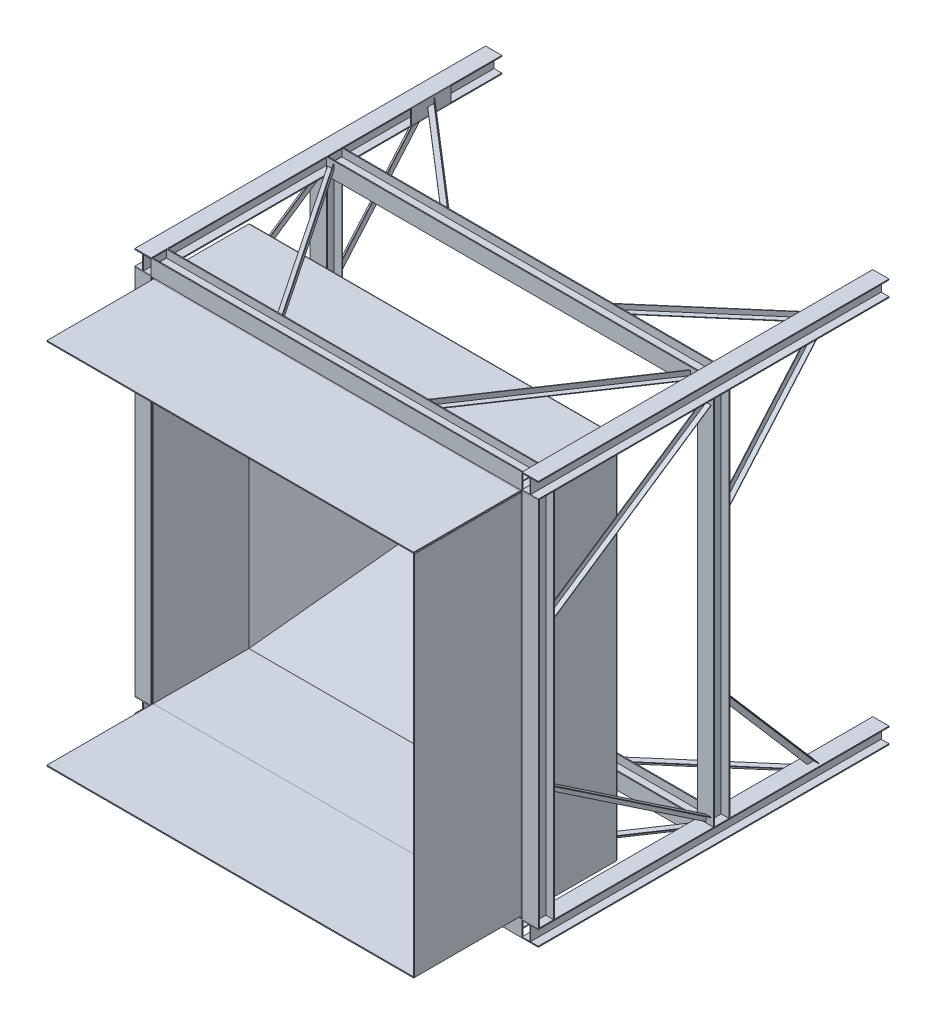
SolidWorks part; units mm, degrees
other "DetailItem1"
other "DetailItem2"
other "DetailItem3"
other "DetailItem4"
other "DetailItem5"
other "DetailItem6"
other "DetailItem7"
other "DetailItem8"
other "DetailItem9"
other "DetailItem10"
other "DetailItem11"
other "DetailItem12"
other "DetailItem13"
other "DetailItem14"
other "DetailItem15"
other "DetailItem16"
other "DetailItem17"
other "DetailItem18"
other "DetailItem19"
other "DetailItem20"
other "DetailItem21"
other "DetailItem22"
other "DetailItem23"
other "DetailItem24"
other "DetailItem25"
other "DetailItem26"
other "DetailItem27"
other "DetailItem28"
other "DetailItem29"
other "DetailItem30"
other "DetailItem31"
other "DetailItem32"
other "DetailItem33"
other "DetailItem34"
other "DetailItem35"
other "DetailItem36"
other "DetailItem37"
other "DetailItem38"
other "DetailItem39"
other "DetailItem40"
other "DetailItem41"
other "DetailItem42"
other "DetailItem43"
other "DetailItem44"
other "DetailItem45"
other "DetailItem46"
other "DetailItem47"
other "DetailItem48"
other "DetailItem49"
other "DetailItem50"
other "DetailItem51"
other "DetailItem52"
other "DetailItem53"
other "DetailItem54"
other "DetailItem55"
other "DetailItem56"
other "DetailItem57"
other "DetailItem58"
other "DetailItem59"
other "DetailItem60"
other "DetailItem61"
other "DetailItem62"
other "DetailItem63"
other "DetailItem64"
other "DetailItem65"
other "DetailItem66"
other "DetailItem67"
other "DetailItem68"
other "DetailItem69"
other "DetailItem70"
other "DetailItem71"
other "DetailItem72"
other "DetailItem73"
other "Carpeta de soldadura"
other "Cordón de soldadura1"
other "Soldadura Viga H carga 1650 B"
other "Soldadura Viga H carga 3300 A"
other "Soldadura Viga H carga 3300 B"
other "Soldadura asiento a tolva carga"
other "Soldadura asiento a bastidor carga"
other "Soldadura Viga H fondo 1650 A"
other "Soldadura Viga H fondo 1650 B"
other "Soldadura Viga H fondo 3300 A"
other "Soldadura Viga H fondo 3300 B"
other "Soldadura asiento a tolva fondo"
other "Soldadura asiento a bastidor fondo"
other "Soldadura Viga H izquierda 1650 A"
other "Soldadura Viga H izquierda 1650 B"
other "Soldadura Viga H izquierda 3300 A"
other "Soldadura Viga H izquierda 3300 B"
other "Soldadura asiento a tolva izquierda"
other "Soldadura asiento a bastidor izquierda"
other "Soldadura Viga H derecha 1650 A"
other "Soldadura Viga H derecha 1650 B"
other "Soldadura Viga H derecha 3300 A"
other "Soldadura Viga H derecha 3300 B"
other "Soldadura asiento a tolva derecha"
other "Soldadura asiento a bastidor derecha"
other "Soldadura Angular superior carga A inferior"
other "Soldadura Angular superior carga A superior"
other "Soldadura Angular inferior carga A inferior"
other "Soldadura Angular inferior carga A superior"
other "Soldadura Angular superior carga B inferior"
other "Soldadura Angular superior carga B superior"
other "Soldadura Angular inferior carga B inferior"
other "Soldadura Angular inferior carga B superior"
other "Soldadura Angular superior fondo A inferior"
other "Soldadura Angular superior fondo A superior"
other "Soldadura Angular inferior fondo A inferior"
other "Soldadura Angular inferior fondo A superior"
other "Soldadura Angular superior fondo B inferior"
other "Soldadura Angular superior fondo B superior"
other "Soldadura Angular inferior fondo B inferior"
other "Soldadura Angular inferior fondo B superior"
other "Soldadura Angular superior izquierda A inferior"
other "Soldadura Angular superior izquierda A superior"
other "Soldadura Angular inferior izquierda A inferior"
other "Soldadura Angular inferior izquierda A superior"
other "Soldadura Angular superior izquierda B inferior"
other "Soldadura Angular superior izquierda B superior"
other "Soldadura Angular inferior izquierda B inferior"
other "Soldadura Angular inferior izquierda B superior"
other "Soldadura Angular superior derecha A inferior"
other "Soldadura Angular superior derecha A superior"
other "Soldadura Angular inferior derecha A inferior"
other "Soldadura Angular inferior derecha A superior"
other "Soldadura Angular superior derecha B inferior"
other "Soldadura Angular superior derecha B superior"
other "Soldadura Angular inferior derecha B inferior"
other "Soldadura Angular inferior derecha B superior"
other "Soldadura alerón a collar lateral Y negativo"
other "Soldadura esquina del collar lateral Y negativo"
other "Soldadura quiebre del embudo lateral Y negativo"
other "Soldadura arista inclinada lateral Y negativo"
other "Soldadura alerón a collar derecha"
other "Soldadura esquina del collar derecha"
other "Soldadura quiebre del embudo derecha"
other "Soldadura arista inclinada derecha"
other "Soldadura alerón a collar lateral Y positivo"
other "Soldadura esquina del collar lateral Y positivo"
other "Soldadura quiebre del embudo lateral Y positivo"
other "Soldadura arista inclinada lateral Y positivo"
other "Soldadura esquina del collar carga"
other "Soldadura quiebre del embudo carga"
other "Soldadura arista inclinada carga"
other "Soldadura esquina alerones derecha"
other "Soldadura esquina alerones sur"
material "ASTM A36 Steel"
ref_plane "Front Plane" through (0, 0, 0) normal (0, 0, 1) x (1, 0, 0)
ref_plane "Top Plane" through (0, 0, 0) normal (0, 1, 0) x (1, 0, 0)
ref_plane "Right Plane" through (0, 0, 0) normal (1, 0, 0) x (0, 0, -1)
sketch3d "Referencias 1"
  point P0 (0, 0, 0)
  point P1 (0, -190, 0)
  point P2 (200, 0, 0)
ref_plane "Plano de perfil 1 estructura" through (0, 0, 0) normal (0, 0, 1) x (1, 0, 0)
sketch "Contorno Columna H 1" plane through (0, 0, 0) normal (0, 0, 1) x (1, 0, 0)
  line L0 (-1898, -1898) -> (-1745, -1898)
  line L1 (-1745, -1898) -> (-1745, -1889)
  line L2 (-1745, -1889) -> (-1818.25, -1889)
  line L3 (-1818.25, -1889) -> (-1818.25, -1754)
  line L4 (-1818.25, -1754) -> (-1745, -1754)
  line L5 (-1745, -1754) -> (-1745, -1745)
  line L6 (-1745, -1745) -> (-1898, -1745)
  line L7 (-1898, -1745) -> (-1898, -1754)
  line L8 (-1898, -1754) -> (-1824.75, -1754)
  line L9 (-1824.75, -1754) -> (-1824.75, -1889)
  line L10 (-1824.75, -1889) -> (-1898, -1889)
  line L11 (-1898, -1889) -> (-1898, -1898)
extrude "Columna H 1" add sketch "Contorno Columna H 1" along normal blind 3300 separate body
sketch "Contorno Columna H 2" plane through (0, 0, 0) normal (0, 0, 1) x (1, 0, 0)
  line L0 (-1898, 1745) -> (-1745, 1745)
  line L1 (-1745, 1745) -> (-1745, 1754)
  line L2 (-1745, 1754) -> (-1818.25, 1754)
  line L3 (-1818.25, 1754) -> (-1818.25, 1889)
  line L4 (-1818.25, 1889) -> (-1745, 1889)
  line L5 (-1745, 1889) -> (-1745, 1898)
  line L6 (-1745, 1898) -> (-1898, 1898)
  line L7 (-1898, 1898) -> (-1898, 1889)
  line L8 (-1898, 1889) -> (-1824.75, 1889)
  line L9 (-1824.75, 1889) -> (-1824.75, 1754)
  line L10 (-1824.75, 1754) -> (-1898, 1754)
  line L11 (-1898, 1754) -> (-1898, 1745)
extrude "Columna H 2" add sketch "Contorno Columna H 2" along normal blind 3300 separate body
sketch "Contorno Columna H 3" plane through (0, 0, 0) normal (0, 0, 1) x (1, 0, 0)
  line L0 (1745, -1898) -> (1898, -1898)
  line L1 (1898, -1898) -> (1898, -1889)
  line L2 (1898, -1889) -> (1824.75, -1889)
  line L3 (1824.75, -1889) -> (1824.75, -1754)
  line L4 (1824.75, -1754) -> (1898, -1754)
  line L5 (1898, -1754) -> (1898, -1745)
  line L6 (1898, -1745) -> (1745, -1745)
  line L7 (1745, -1745) -> (1745, -1754)
  line L8 (1745, -1754) -> (1818.25, -1754)
  line L9 (1818.25, -1754) -> (1818.25, -1889)
  line L10 (1818.25, -1889) -> (1745, -1889)
  line L11 (1745, -1889) -> (1745, -1898)
extrude "Columna H 3" add sketch "Contorno Columna H 3" along normal blind 3300 separate body
sketch "Contorno Columna H 4" plane through (0, 0, 0) normal (0, 0, 1) x (1, 0, 0)
  line L0 (1745, 1745) -> (1898, 1745)
  line L1 (1898, 1745) -> (1898, 1754)
  line L2 (1898, 1754) -> (1824.75, 1754)
  line L3 (1824.75, 1754) -> (1824.75, 1889)
  line L4 (1824.75, 1889) -> (1898, 1889)
  line L5 (1898, 1889) -> (1898, 1898)
  line L6 (1898, 1898) -> (1745, 1898)
  line L7 (1745, 1898) -> (1745, 1889)
  line L8 (1745, 1889) -> (1818.25, 1889)
  line L9 (1818.25, 1889) -> (1818.25, 1754)
  line L10 (1818.25, 1754) -> (1745, 1754)
  line L11 (1745, 1754) -> (1745, 1745)
extrude "Columna H 4" add sketch "Contorno Columna H 4" along normal blind 3300 separate body
sketch3d "Referencias 2"
  point P0 (-1745, 0, 0)
  point P1 (-1745, 190, 0)
  point P2 (-1745, 0, 200)
ref_plane "Plano de perfil 2 estructura" through (-1745, 0, 0) normal (1, 0, 0) x (0, 0, -1)
sketch "Contorno Viga H carga 1650" plane through (-1745, 0, 0) normal (1, 0, 0) x (0, 0, -1)
  line L0 (-1497, -1745) -> (-1497, -1898)
  line L1 (-1497, -1898) -> (-1506, -1898)
  line L2 (-1506, -1898) -> (-1506, -1824.75)
  line L3 (-1506, -1824.75) -> (-1641, -1824.75)
  line L4 (-1641, -1824.75) -> (-1641, -1898)
  line L5 (-1641, -1898) -> (-1650, -1898)
  line L6 (-1650, -1898) -> (-1650, -1745)
  line L7 (-1650, -1745) -> (-1641, -1745)
  line L8 (-1641, -1745) -> (-1641, -1818.25)
  line L9 (-1641, -1818.25) -> (-1506, -1818.25)
  line L10 (-1506, -1818.25) -> (-1506, -1745)
  line L11 (-1506, -1745) -> (-1497, -1745)
extrude "Viga H carga 1650" add sketch "Contorno Viga H carga 1650" along normal blind 3490 separate body
sketch "Contorno Viga H carga 3300" plane through (-1745, 0, 0) normal (1, 0, 0) x (0, 0, -1)
  line L0 (-3147, -1745) -> (-3147, -1898)
  line L1 (-3147, -1898) -> (-3156, -1898)
  line L2 (-3156, -1898) -> (-3156, -1824.75)
  line L3 (-3156, -1824.75) -> (-3291, -1824.75)
  line L4 (-3291, -1824.75) -> (-3291, -1898)
  line L5 (-3291, -1898) -> (-3300, -1898)
  line L6 (-3300, -1898) -> (-3300, -1745)
  line L7 (-3300, -1745) -> (-3291, -1745)
  line L8 (-3291, -1745) -> (-3291, -1818.25)
  line L9 (-3291, -1818.25) -> (-3156, -1818.25)
  line L10 (-3156, -1818.25) -> (-3156, -1745)
  line L11 (-3156, -1745) -> (-3147, -1745)
extrude "Viga H carga 3300" add sketch "Contorno Viga H carga 3300" along normal blind 3490 separate body
sketch "Contorno Cierre columna carga A" plane through (-1745, 0, 0) normal (1, 0, 0) x (0, 0, -1)
  line L0 (-480, -1754) -> (-480, -1889)
  line L1 (-480, -1889) -> (-850, -1889)
  line L2 (-850, -1889) -> (-850, -1754)
  line L3 (-850, -1754) -> (-480, -1754)
extrude "Cierre columna carga A" add sketch "Contorno Cierre columna carga A" against normal blind 8 separate body
sketch3d "Referencias 3"
  point P0 (0, -1821.5, 0)
  point P1 (-190, -1821.5, 0)
  point P2 (0, -1821.5, 200)
ref_plane "Plano de perfil 3 estructura" through (0, -1821.5, 0) normal (0, 1, 0) x (1, 0, 0)
sketch "Contorno Ala plana Angular superior carga A" plane through (0, -1821.5, 0) normal (0, 1, 0) x (1, 0, 0)
  line L0 (-1674.8701, -1650) -> (-1735.1299, -1650)
  line L1 (-1735.1299, -1650) -> (-728.1299, -3147)
  line L2 (-728.1299, -3147) -> (-667.8701, -3147)
  line L3 (-667.8701, -3147) -> (-1674.8701, -1650)
extrude "Ala plana Angular superior carga A" add sketch "Contorno Ala plana Angular superior carga A" against normal blind 5 separate body
sketch3d "Referencias 4"
  point P0 (0, -1826.5, 0)
  point P1 (-190, -1826.5, 0)
  point P2 (0, -1826.5, 200)
ref_plane "Plano de perfil 4 estructura" through (0, -1826.5, 0) normal (0, 1, 0) x (1, 0, 0)
sketch "Contorno Retorno Angular superior carga A" plane through (0, -1826.5, 0) normal (0, 1, 0) x (1, 0, 0)
  line L0 (-1674.8701, -1650) -> (-1680.8961, -1650)
  line L1 (-1680.8961, -1650) -> (-673.8961, -3147)
  line L2 (-673.8961, -3147) -> (-667.8701, -3147)
  line L3 (-667.8701, -3147) -> (-1674.8701, -1650)
extrude "Retorno Angular superior carga A" add sketch "Contorno Retorno Angular superior carga A" against normal blind 45 separate body
combine bodies "Angular superior carga A" operation type add bodies to combine 108 109
sketch "Contorno Ala plana Angular inferior carga A" plane through (0, -1821.5, 0) normal (0, 1, 0) x (1, 0, 0)
  line L0 (-1745, -631.991) -> (-1745, -698.009)
  line L1 (-1745, -698.009) -> (-818.2856, -1497)
  line L2 (-818.2856, -1497) -> (-741.7144, -1497)
  line L3 (-741.7144, -1497) -> (-1745, -631.991)
extrude "Ala plana Angular inferior carga A" add sketch "Contorno Ala plana Angular inferior carga A" against normal blind 5 separate body
sketch "Contorno Retorno Angular inferior carga A" plane through (0, -1826.5, 0) normal (0, 1, 0) x (1, 0, 0)
  line L0 (-1745, -631.991) -> (-1745, -638.5928)
  line L1 (-1745, -638.5928) -> (-749.3715, -1497)
  line L2 (-749.3715, -1497) -> (-741.7144, -1497)
  line L3 (-741.7144, -1497) -> (-1745, -631.991)
extrude "Retorno Angular inferior carga A" add sketch "Contorno Retorno Angular inferior carga A" against normal blind 45 separate body
combine bodies "Angular inferior carga A" operation type add bodies to combine 111 112
sketch3d "Referencias 5"
  point P0 (1745, 0, 0)
  point P1 (1745, 190, 0)
  point P2 (1745, 0, 200)
ref_plane "Plano de perfil 5 estructura" through (1745, 0, 0) normal (1, 0, 0) x (0, 0, -1)
sketch "Contorno Cierre columna carga B" plane through (1745, 0, 0) normal (1, 0, 0) x (0, 0, -1)
  line L0 (-480, -1754) -> (-480, -1889)
  line L1 (-480, -1889) -> (-850, -1889)
  line L2 (-850, -1889) -> (-850, -1754)
  line L3 (-850, -1754) -> (-480, -1754)
extrude "Cierre columna carga B" add sketch "Contorno Cierre columna carga B" along normal blind 8 separate body
sketch "Contorno Ala plana Angular superior carga B" plane through (0, -1821.5, 0) normal (0, 1, 0) x (1, 0, 0)
  line L0 (1674.8701, -1650) -> (1735.1299, -1650)
  line L1 (1735.1299, -1650) -> (728.1299, -3147)
  line L2 (728.1299, -3147) -> (667.8701, -3147)
  line L3 (667.8701, -3147) -> (1674.8701, -1650)
extrude "Ala plana Angular superior carga B" add sketch "Contorno Ala plana Angular superior carga B" against normal blind 5 separate body
sketch "Contorno Retorno Angular superior carga B" plane through (0, -1826.5, 0) normal (0, 1, 0) x (1, 0, 0)
  line L0 (1674.8701, -1650) -> (1680.8961, -1650)
  line L1 (1680.8961, -1650) -> (673.8961, -3147)
  line L2 (673.8961, -3147) -> (667.8701, -3147)
  line L3 (667.8701, -3147) -> (1674.8701, -1650)
extrude "Retorno Angular superior carga B" add sketch "Contorno Retorno Angular superior carga B" against normal blind 45 separate body
combine bodies "Angular superior carga B" operation type add bodies to combine 115 116
sketch "Contorno Ala plana Angular inferior carga B" plane through (0, -1821.5, 0) normal (0, 1, 0) x (1, 0, 0)
  line L0 (1745, -631.991) -> (1745, -698.009)
  line L1 (1745, -698.009) -> (818.2856, -1497)
  line L2 (818.2856, -1497) -> (741.7144, -1497)
  line L3 (741.7144, -1497) -> (1745, -631.991)
extrude "Ala plana Angular inferior carga B" add sketch "Contorno Ala plana Angular inferior carga B" against normal blind 5 separate body
sketch "Contorno Retorno Angular inferior carga B" plane through (0, -1826.5, 0) normal (0, 1, 0) x (1, 0, 0)
  line L0 (1745, -631.991) -> (1745, -638.5928)
  line L1 (1745, -638.5928) -> (749.3715, -1497)
  line L2 (749.3715, -1497) -> (741.7144, -1497)
  line L3 (741.7144, -1497) -> (1745, -631.991)
extrude "Retorno Angular inferior carga B" add sketch "Contorno Retorno Angular inferior carga B" against normal blind 45 separate body
combine bodies "Angular inferior carga B" operation type add bodies to combine 118 119
sketch3d "Referencias 6"
  point P0 (0, 0, 3281.475)
  point P1 (0, -190, 3281.475)
  point P2 (200, 0, 3281.475)
ref_plane "Plano de perfil 6 estructura" through (0, 0, 3281.475) normal (0, 0, 1) x (1, 0, 0)
sketch "Contorno Asiento soldado carga" plane through (0, 0, 3281.475) normal (0, 0, 1) x (1, 0, 0)
  line L0 (-1450, -1734.525) -> (1450, -1734.525)
  line L1 (1450, -1734.525) -> (1450, -1818.25)
  line L2 (1450, -1818.25) -> (-1450, -1818.25)
  line L3 (-1450, -1818.25) -> (-1450, -1734.525)
extrude "Asiento soldado carga" add sketch "Contorno Asiento soldado carga" along normal blind 9.525 separate body
sketch "Contorno Viga H fondo 1650" plane through (-1745, 0, 0) normal (1, 0, 0) x (0, 0, -1)
  line L0 (-1497, 1745) -> (-1497, 1898)
  line L1 (-1497, 1898) -> (-1506, 1898)
  line L2 (-1506, 1898) -> (-1506, 1824.75)
  line L3 (-1506, 1824.75) -> (-1641, 1824.75)
  line L4 (-1641, 1824.75) -> (-1641, 1898)
  line L5 (-1641, 1898) -> (-1650, 1898)
  line L6 (-1650, 1898) -> (-1650, 1745)
  line L7 (-1650, 1745) -> (-1641, 1745)
  line L8 (-1641, 1745) -> (-1641, 1818.25)
  line L9 (-1641, 1818.25) -> (-1506, 1818.25)
  line L10 (-1506, 1818.25) -> (-1506, 1745)
  line L11 (-1506, 1745) -> (-1497, 1745)
extrude "Viga H fondo 1650" add sketch "Contorno Viga H fondo 1650" along normal blind 3490 separate body
sketch "Contorno Viga H fondo 3300" plane through (-1745, 0, 0) normal (1, 0, 0) x (0, 0, -1)
  line L0 (-3147, 1745) -> (-3147, 1898)
  line L1 (-3147, 1898) -> (-3156, 1898)
  line L2 (-3156, 1898) -> (-3156, 1824.75)
  line L3 (-3156, 1824.75) -> (-3291, 1824.75)
  line L4 (-3291, 1824.75) -> (-3291, 1898)
  line L5 (-3291, 1898) -> (-3300, 1898)
  line L6 (-3300, 1898) -> (-3300, 1745)
  line L7 (-3300, 1745) -> (-3291, 1745)
  line L8 (-3291, 1745) -> (-3291, 1818.25)
  line L9 (-3291, 1818.25) -> (-3156, 1818.25)
  line L10 (-3156, 1818.25) -> (-3156, 1745)
  line L11 (-3156, 1745) -> (-3147, 1745)
extrude "Viga H fondo 3300" add sketch "Contorno Viga H fondo 3300" along normal blind 3490 separate body
sketch "Contorno Cierre columna fondo A" plane through (-1745, 0, 0) normal (1, 0, 0) x (0, 0, -1)
  line L0 (-480, 1754) -> (-480, 1889)
  line L1 (-480, 1889) -> (-850, 1889)
  line L2 (-850, 1889) -> (-850, 1754)
  line L3 (-850, 1754) -> (-480, 1754)
extrude "Cierre columna fondo A" add sketch "Contorno Cierre columna fondo A" against normal blind 8 separate body
sketch3d "Referencias 7"
  point P0 (0, 1821.5, 0)
  point P1 (-190, 1821.5, 0)
  point P2 (0, 1821.5, 200)
ref_plane "Plano de perfil 7 estructura" through (0, 1821.5, 0) normal (0, 1, 0) x (1, 0, 0)
sketch "Contorno Ala plana Angular superior fondo A" plane through (0, 1821.5, 0) normal (0, 1, 0) x (1, 0, 0)
  line L0 (-1674.8701, -1650) -> (-1735.1299, -1650)
  line L1 (-1735.1299, -1650) -> (-728.1299, -3147)
  line L2 (-728.1299, -3147) -> (-667.8701, -3147)
  line L3 (-667.8701, -3147) -> (-1674.8701, -1650)
extrude "Ala plana Angular superior fondo A" add sketch "Contorno Ala plana Angular superior fondo A" along normal blind 5 separate body
sketch3d "Referencias 8"
  point P0 (0, 1826.5, 0)
  point P1 (-190, 1826.5, 0)
  point P2 (0, 1826.5, 200)
ref_plane "Plano de perfil 8 estructura" through (0, 1826.5, 0) normal (0, 1, 0) x (1, 0, 0)
sketch "Contorno Retorno Angular superior fondo A" plane through (0, 1826.5, 0) normal (0, 1, 0) x (1, 0, 0)
  line L0 (-1674.8701, -1650) -> (-1680.8961, -1650)
  line L1 (-1680.8961, -1650) -> (-673.8961, -3147)
  line L2 (-673.8961, -3147) -> (-667.8701, -3147)
  line L3 (-667.8701, -3147) -> (-1674.8701, -1650)
extrude "Retorno Angular superior fondo A" add sketch "Contorno Retorno Angular superior fondo A" along normal blind 45 separate body
combine bodies "Angular superior fondo A" operation type add bodies to combine 125 126
sketch "Contorno Ala plana Angular inferior fondo A" plane through (0, 1821.5, 0) normal (0, 1, 0) x (1, 0, 0)
  line L0 (-1745, -631.991) -> (-1745, -698.009)
  line L1 (-1745, -698.009) -> (-818.2856, -1497)
  line L2 (-818.2856, -1497) -> (-741.7144, -1497)
  line L3 (-741.7144, -1497) -> (-1745, -631.991)
extrude "Ala plana Angular inferior fondo A" add sketch "Contorno Ala plana Angular inferior fondo A" along normal blind 5 separate body
sketch "Contorno Retorno Angular inferior fondo A" plane through (0, 1826.5, 0) normal (0, 1, 0) x (1, 0, 0)
  line L0 (-1745, -631.991) -> (-1745, -638.5928)
  line L1 (-1745, -638.5928) -> (-749.3715, -1497)
  line L2 (-749.3715, -1497) -> (-741.7144, -1497)
  line L3 (-741.7144, -1497) -> (-1745, -631.991)
extrude "Retorno Angular inferior fondo A" add sketch "Contorno Retorno Angular inferior fondo A" along normal blind 45 separate body
combine bodies "Angular inferior fondo A" operation type add bodies to combine 128 129
sketch "Contorno Cierre columna fondo B" plane through (1745, 0, 0) normal (1, 0, 0) x (0, 0, -1)
  line L0 (-480, 1754) -> (-480, 1889)
  line L1 (-480, 1889) -> (-850, 1889)
  line L2 (-850, 1889) -> (-850, 1754)
  line L3 (-850, 1754) -> (-480, 1754)
extrude "Cierre columna fondo B" add sketch "Contorno Cierre columna fondo B" along normal blind 8 separate body
sketch "Contorno Ala plana Angular superior fondo B" plane through (0, 1821.5, 0) normal (0, 1, 0) x (1, 0, 0)
  line L0 (1674.8701, -1650) -> (1735.1299, -1650)
  line L1 (1735.1299, -1650) -> (728.1299, -3147)
  line L2 (728.1299, -3147) -> (667.8701, -3147)
  line L3 (667.8701, -3147) -> (1674.8701, -1650)
extrude "Ala plana Angular superior fondo B" add sketch "Contorno Ala plana Angular superior fondo B" along normal blind 5 separate body
sketch "Contorno Retorno Angular superior fondo B" plane through (0, 1826.5, 0) normal (0, 1, 0) x (1, 0, 0)
  line L0 (1674.8701, -1650) -> (1680.8961, -1650)
  line L1 (1680.8961, -1650) -> (673.8961, -3147)
  line L2 (673.8961, -3147) -> (667.8701, -3147)
  line L3 (667.8701, -3147) -> (1674.8701, -1650)
extrude "Retorno Angular superior fondo B" add sketch "Contorno Retorno Angular superior fondo B" along normal blind 45 separate body
combine bodies "Angular superior fondo B" operation type add bodies to combine 132 133
sketch "Contorno Ala plana Angular inferior fondo B" plane through (0, 1821.5, 0) normal (0, 1, 0) x (1, 0, 0)
  line L0 (1745, -631.991) -> (1745, -698.009)
  line L1 (1745, -698.009) -> (818.2856, -1497)
  line L2 (818.2856, -1497) -> (741.7144, -1497)
  line L3 (741.7144, -1497) -> (1745, -631.991)
extrude "Ala plana Angular inferior fondo B" add sketch "Contorno Ala plana Angular inferior fondo B" along normal blind 5 separate body
sketch "Contorno Retorno Angular inferior fondo B" plane through (0, 1826.5, 0) normal (0, 1, 0) x (1, 0, 0)
  line L0 (1745, -631.991) -> (1745, -638.5928)
  line L1 (1745, -638.5928) -> (749.3715, -1497)
  line L2 (749.3715, -1497) -> (741.7144, -1497)
  line L3 (741.7144, -1497) -> (1745, -631.991)
extrude "Retorno Angular inferior fondo B" add sketch "Contorno Retorno Angular inferior fondo B" along normal blind 45 separate body
combine bodies "Angular inferior fondo B" operation type add bodies to combine 135 136
sketch "Contorno Asiento soldado fondo" plane through (0, 0, 3281.475) normal (0, 0, 1) x (1, 0, 0)
  line L0 (-1450, 1734.525) -> (1450, 1734.525)
  line L1 (1450, 1734.525) -> (1450, 1818.25)
  line L2 (1450, 1818.25) -> (-1450, 1818.25)
  line L3 (-1450, 1818.25) -> (-1450, 1734.525)
extrude "Asiento soldado fondo" add sketch "Contorno Asiento soldado fondo" along normal blind 9.525 separate body
sketch3d "Referencias 9"
  point P0 (0, -1745, 0)
  point P1 (-190, -1745, 0)
  point P2 (0, -1745, 200)
ref_plane "Plano de perfil 9 estructura" through (0, -1745, 0) normal (0, 1, 0) x (1, 0, 0)
sketch "Contorno Viga H izquierda 1650" plane through (0, -1745, 0) normal (0, 1, 0) x (1, 0, 0)
  line L0 (-1745, -1497) -> (-1898, -1497)
  line L1 (-1898, -1497) -> (-1898, -1506)
  line L2 (-1898, -1506) -> (-1824.75, -1506)
  line L3 (-1824.75, -1506) -> (-1824.75, -1641)
  line L4 (-1824.75, -1641) -> (-1898, -1641)
  line L5 (-1898, -1641) -> (-1898, -1650)
  line L6 (-1898, -1650) -> (-1745, -1650)
  line L7 (-1745, -1650) -> (-1745, -1641)
  line L8 (-1745, -1641) -> (-1818.25, -1641)
  line L9 (-1818.25, -1641) -> (-1818.25, -1506)
  line L10 (-1818.25, -1506) -> (-1745, -1506)
  line L11 (-1745, -1506) -> (-1745, -1497)
extrude "Viga H izquierda 1650" add sketch "Contorno Viga H izquierda 1650" along normal blind 3490 separate body
sketch "Contorno Viga H izquierda 3300" plane through (0, -1745, 0) normal (0, 1, 0) x (1, 0, 0)
  line L0 (-1745, -3147) -> (-1898, -3147)
  line L1 (-1898, -3147) -> (-1898, -3156)
  line L2 (-1898, -3156) -> (-1824.75, -3156)
  line L3 (-1824.75, -3156) -> (-1824.75, -3291)
  line L4 (-1824.75, -3291) -> (-1898, -3291)
  line L5 (-1898, -3291) -> (-1898, -3300)
  line L6 (-1898, -3300) -> (-1745, -3300)
  line L7 (-1745, -3300) -> (-1745, -3291)
  line L8 (-1745, -3291) -> (-1818.25, -3291)
  line L9 (-1818.25, -3291) -> (-1818.25, -3156)
  line L10 (-1818.25, -3156) -> (-1745, -3156)
  line L11 (-1745, -3156) -> (-1745, -3147)
extrude "Viga H izquierda 3300" add sketch "Contorno Viga H izquierda 3300" along normal blind 3490 separate body
sketch3d "Referencias 10"
  point P0 (-1821.5, 0, 0)
  point P1 (-1821.5, 190, 0)
  point P2 (-1821.5, 0, 200)
ref_plane "Plano de perfil 10 estructura" through (-1821.5, 0, 0) normal (1, 0, 0) x (0, 0, -1)
sketch "Contorno Ala plana Angular superior izquierda A" plane through (-1821.5, 0, 0) normal (1, 0, 0) x (0, 0, -1)
  line L0 (-1650, -1674.8701) -> (-1650, -1735.1299)
  line L1 (-1650, -1735.1299) -> (-3147, -728.1299)
  line L2 (-3147, -728.1299) -> (-3147, -667.8701)
  line L3 (-3147, -667.8701) -> (-1650, -1674.8701)
extrude "Ala plana Angular superior izquierda A" add sketch "Contorno Ala plana Angular superior izquierda A" against normal blind 5 separate body
sketch3d "Referencias 11"
  point P0 (-1826.5, 0, 0)
  point P1 (-1826.5, 190, 0)
  point P2 (-1826.5, 0, 200)
ref_plane "Plano de perfil 11 estructura" through (-1826.5, 0, 0) normal (1, 0, 0) x (0, 0, -1)
sketch "Contorno Retorno Angular superior izquierda A" plane through (-1826.5, 0, 0) normal (1, 0, 0) x (0, 0, -1)
  line L0 (-1650, -1674.8701) -> (-1650, -1680.8961)
  line L1 (-1650, -1680.8961) -> (-3147, -673.8961)
  line L2 (-3147, -673.8961) -> (-3147, -667.8701)
  line L3 (-3147, -667.8701) -> (-1650, -1674.8701)
extrude "Retorno Angular superior izquierda A" add sketch "Contorno Retorno Angular superior izquierda A" against normal blind 45 separate body
combine bodies "Angular superior izquierda A" operation type add bodies to combine 141 142
sketch "Contorno Ala plana Angular inferior izquierda A" plane through (-1821.5, 0, 0) normal (1, 0, 0) x (0, 0, -1)
  line L0 (-631.991, -1745) -> (-698.009, -1745)
  line L1 (-698.009, -1745) -> (-1497, -818.2856)
  line L2 (-1497, -818.2856) -> (-1497, -741.7144)
  line L3 (-1497, -741.7144) -> (-631.991, -1745)
extrude "Ala plana Angular inferior izquierda A" add sketch "Contorno Ala plana Angular inferior izquierda A" against normal blind 5 separate body
sketch "Contorno Retorno Angular inferior izquierda A" plane through (-1826.5, 0, 0) normal (1, 0, 0) x (0, 0, -1)
  line L0 (-631.991, -1745) -> (-638.5928, -1745)
  line L1 (-638.5928, -1745) -> (-1497, -749.3715)
  line L2 (-1497, -749.3715) -> (-1497, -741.7144)
  line L3 (-1497, -741.7144) -> (-631.991, -1745)
extrude "Retorno Angular inferior izquierda A" add sketch "Contorno Retorno Angular inferior izquierda A" against normal blind 45 separate body
combine bodies "Angular inferior izquierda A" operation type add bodies to combine 144 145
sketch "Contorno Ala plana Angular superior izquierda B" plane through (-1821.5, 0, 0) normal (1, 0, 0) x (0, 0, -1)
  line L0 (-1650, 1674.8701) -> (-1650, 1735.1299)
  line L1 (-1650, 1735.1299) -> (-3147, 728.1299)
  line L2 (-3147, 728.1299) -> (-3147, 667.8701)
  line L3 (-3147, 667.8701) -> (-1650, 1674.8701)
extrude "Ala plana Angular superior izquierda B" add sketch "Contorno Ala plana Angular superior izquierda B" against normal blind 5 separate body
sketch "Contorno Retorno Angular superior izquierda B" plane through (-1826.5, 0, 0) normal (1, 0, 0) x (0, 0, -1)
  line L0 (-1650, 1674.8701) -> (-1650, 1680.8961)
  line L1 (-1650, 1680.8961) -> (-3147, 673.8961)
  line L2 (-3147, 673.8961) -> (-3147, 667.8701)
  line L3 (-3147, 667.8701) -> (-1650, 1674.8701)
extrude "Retorno Angular superior izquierda B" add sketch "Contorno Retorno Angular superior izquierda B" against normal blind 45 separate body
combine bodies "Angular superior izquierda B" operation type add bodies to combine 147 148
sketch "Contorno Ala plana Angular inferior izquierda B" plane through (-1821.5, 0, 0) normal (1, 0, 0) x (0, 0, -1)
  line L0 (-631.991, 1745) -> (-698.009, 1745)
  line L1 (-698.009, 1745) -> (-1497, 818.2856)
  line L2 (-1497, 818.2856) -> (-1497, 741.7144)
  line L3 (-1497, 741.7144) -> (-631.991, 1745)
extrude "Ala plana Angular inferior izquierda B" add sketch "Contorno Ala plana Angular inferior izquierda B" against normal blind 5 separate body
sketch "Contorno Retorno Angular inferior izquierda B" plane through (-1826.5, 0, 0) normal (1, 0, 0) x (0, 0, -1)
  line L0 (-631.991, 1745) -> (-638.5928, 1745)
  line L1 (-638.5928, 1745) -> (-1497, 749.3715)
  line L2 (-1497, 749.3715) -> (-1497, 741.7144)
  line L3 (-1497, 741.7144) -> (-631.991, 1745)
extrude "Retorno Angular inferior izquierda B" add sketch "Contorno Retorno Angular inferior izquierda B" against normal blind 45 separate body
combine bodies "Angular inferior izquierda B" operation type add bodies to combine 150 151
sketch "Contorno Asiento soldado izquierda" plane through (0, 0, 3281.475) normal (0, 0, 1) x (1, 0, 0)
  line L0 (-1734.525, -1450) -> (-1734.525, 1450)
  line L1 (-1734.525, 1450) -> (-1818.25, 1450)
  line L2 (-1818.25, 1450) -> (-1818.25, -1450)
  line L3 (-1818.25, -1450) -> (-1734.525, -1450)
extrude "Asiento soldado izquierda" add sketch "Contorno Asiento soldado izquierda" along normal blind 9.525 separate body
sketch "Contorno Viga H derecha 1650" plane through (0, -1745, 0) normal (0, 1, 0) x (1, 0, 0)
  line L0 (1745, -1497) -> (1898, -1497)
  line L1 (1898, -1497) -> (1898, -1506)
  line L2 (1898, -1506) -> (1824.75, -1506)
  line L3 (1824.75, -1506) -> (1824.75, -1641)
  line L4 (1824.75, -1641) -> (1898, -1641)
  line L5 (1898, -1641) -> (1898, -1650)
  line L6 (1898, -1650) -> (1745, -1650)
  line L7 (1745, -1650) -> (1745, -1641)
  line L8 (1745, -1641) -> (1818.25, -1641)
  line L9 (1818.25, -1641) -> (1818.25, -1506)
  line L10 (1818.25, -1506) -> (1745, -1506)
  line L11 (1745, -1506) -> (1745, -1497)
extrude "Viga H derecha 1650" add sketch "Contorno Viga H derecha 1650" along normal blind 3490 separate body
sketch "Contorno Viga H derecha 3300" plane through (0, -1745, 0) normal (0, 1, 0) x (1, 0, 0)
  line L0 (1745, -3147) -> (1898, -3147)
  line L1 (1898, -3147) -> (1898, -3156)
  line L2 (1898, -3156) -> (1824.75, -3156)
  line L3 (1824.75, -3156) -> (1824.75, -3291)
  line L4 (1824.75, -3291) -> (1898, -3291)
  line L5 (1898, -3291) -> (1898, -3300)
  line L6 (1898, -3300) -> (1745, -3300)
  line L7 (1745, -3300) -> (1745, -3291)
  line L8 (1745, -3291) -> (1818.25, -3291)
  line L9 (1818.25, -3291) -> (1818.25, -3156)
  line L10 (1818.25, -3156) -> (1745, -3156)
  line L11 (1745, -3156) -> (1745, -3147)
extrude "Viga H derecha 3300" add sketch "Contorno Viga H derecha 3300" along normal blind 3490 separate body
sketch3d "Referencias 12"
  point P0 (1821.5, 0, 0)
  point P1 (1821.5, 190, 0)
  point P2 (1821.5, 0, 200)
ref_plane "Plano de perfil 12 estructura" through (1821.5, 0, 0) normal (1, 0, 0) x (0, 0, -1)
sketch "Contorno Ala plana Angular superior derecha A" plane through (1821.5, 0, 0) normal (1, 0, 0) x (0, 0, -1)
  line L0 (-1650, -1674.8701) -> (-1650, -1735.1299)
  line L1 (-1650, -1735.1299) -> (-3147, -728.1299)
  line L2 (-3147, -728.1299) -> (-3147, -667.8701)
  line L3 (-3147, -667.8701) -> (-1650, -1674.8701)
extrude "Ala plana Angular superior derecha A" add sketch "Contorno Ala plana Angular superior derecha A" along normal blind 5 separate body
sketch3d "Referencias 13"
  point P0 (1826.5, 0, 0)
  point P1 (1826.5, 190, 0)
  point P2 (1826.5, 0, 200)
ref_plane "Plano de perfil 13 estructura" through (1826.5, 0, 0) normal (1, 0, 0) x (0, 0, -1)
sketch "Contorno Retorno Angular superior derecha A" plane through (1826.5, 0, 0) normal (1, 0, 0) x (0, 0, -1)
  line L0 (-1650, -1674.8701) -> (-1650, -1680.8961)
  line L1 (-1650, -1680.8961) -> (-3147, -673.8961)
  line L2 (-3147, -673.8961) -> (-3147, -667.8701)
  line L3 (-3147, -667.8701) -> (-1650, -1674.8701)
extrude "Retorno Angular superior derecha A" add sketch "Contorno Retorno Angular superior derecha A" along normal blind 45 separate body
combine bodies "Angular superior derecha A" operation type add bodies to combine 156 157
sketch "Contorno Ala plana Angular inferior derecha A" plane through (1821.5, 0, 0) normal (1, 0, 0) x (0, 0, -1)
  line L0 (-631.991, -1745) -> (-698.009, -1745)
  line L1 (-698.009, -1745) -> (-1497, -818.2856)
  line L2 (-1497, -818.2856) -> (-1497, -741.7144)
  line L3 (-1497, -741.7144) -> (-631.991, -1745)
extrude "Ala plana Angular inferior derecha A" add sketch "Contorno Ala plana Angular inferior derecha A" along normal blind 5 separate body
sketch "Contorno Retorno Angular inferior derecha A" plane through (1826.5, 0, 0) normal (1, 0, 0) x (0, 0, -1)
  line L0 (-631.991, -1745) -> (-638.5928, -1745)
  line L1 (-638.5928, -1745) -> (-1497, -749.3715)
  line L2 (-1497, -749.3715) -> (-1497, -741.7144)
  line L3 (-1497, -741.7144) -> (-631.991, -1745)
extrude "Retorno Angular inferior derecha A" add sketch "Contorno Retorno Angular inferior derecha A" along normal blind 45 separate body
combine bodies "Angular inferior derecha A" operation type add bodies to combine 159 160
sketch "Contorno Ala plana Angular superior derecha B" plane through (1821.5, 0, 0) normal (1, 0, 0) x (0, 0, -1)
  line L0 (-1650, 1674.8701) -> (-1650, 1735.1299)
  line L1 (-1650, 1735.1299) -> (-3147, 728.1299)
  line L2 (-3147, 728.1299) -> (-3147, 667.8701)
  line L3 (-3147, 667.8701) -> (-1650, 1674.8701)
extrude "Ala plana Angular superior derecha B" add sketch "Contorno Ala plana Angular superior derecha B" along normal blind 5 separate body
sketch "Contorno Retorno Angular superior derecha B" plane through (1826.5, 0, 0) normal (1, 0, 0) x (0, 0, -1)
  line L0 (-1650, 1674.8701) -> (-1650, 1680.8961)
  line L1 (-1650, 1680.8961) -> (-3147, 673.8961)
  line L2 (-3147, 673.8961) -> (-3147, 667.8701)
  line L3 (-3147, 667.8701) -> (-1650, 1674.8701)
extrude "Retorno Angular superior derecha B" add sketch "Contorno Retorno Angular superior derecha B" along normal blind 45 separate body
combine bodies "Angular superior derecha B" operation type add bodies to combine 162 163
sketch "Contorno Ala plana Angular inferior derecha B" plane through (1821.5, 0, 0) normal (1, 0, 0) x (0, 0, -1)
  line L0 (-631.991, 1745) -> (-698.009, 1745)
  line L1 (-698.009, 1745) -> (-1497, 818.2856)
  line L2 (-1497, 818.2856) -> (-1497, 741.7144)
  line L3 (-1497, 741.7144) -> (-631.991, 1745)
extrude "Ala plana Angular inferior derecha B" add sketch "Contorno Ala plana Angular inferior derecha B" along normal blind 5 separate body
sketch "Contorno Retorno Angular inferior derecha B" plane through (1826.5, 0, 0) normal (1, 0, 0) x (0, 0, -1)
  line L0 (-631.991, 1745) -> (-638.5928, 1745)
  line L1 (-638.5928, 1745) -> (-1497, 749.3715)
  line L2 (-1497, 749.3715) -> (-1497, 741.7144)
  line L3 (-1497, 741.7144) -> (-631.991, 1745)
extrude "Retorno Angular inferior derecha B" add sketch "Contorno Retorno Angular inferior derecha B" along normal blind 45 separate body
combine bodies "Angular inferior derecha B" operation type add bodies to combine 165 166
sketch "Contorno Asiento soldado derecha" plane through (0, 0, 3281.475) normal (0, 0, 1) x (1, 0, 0)
  line L0 (1734.525, -1450) -> (1734.525, 1450)
  line L1 (1734.525, 1450) -> (1818.25, 1450)
  line L2 (1818.25, 1450) -> (1818.25, -1450)
  line L3 (1818.25, -1450) -> (1734.525, -1450)
extrude "Asiento soldado derecha" add sketch "Contorno Asiento soldado derecha" along normal blind 9.525 separate body
sketch3d "Junta Viga H carga 1650 A"
  line L0 (-1745, -1745, 1650) -> (-1745, -1898, 1650)
sketch3d "Junta Viga H carga 1650 B"
  line L0 (1745, -1745, 1650) -> (1745, -1898, 1650)
sketch3d "Junta Viga H carga 3300 A"
  line L0 (-1745, -1745, 3300) -> (-1745, -1898, 3300)
sketch3d "Junta Viga H carga 3300 B"
  line L0 (1745, -1745, 3300) -> (1745, -1898, 3300)
sketch3d "Junta Angular superior carga A inferior"
  line L0 (-1674.8701, -1821.5, 1650) -> (-1735.1299, -1821.5, 1650)
sketch3d "Junta Angular superior carga A superior"
  line L0 (-667.8701, -1821.5, 3147) -> (-728.1299, -1821.5, 3147)
sketch3d "Junta Angular inferior carga A inferior"
  line L0 (-1745, -1821.5, 631.991) -> (-1745, -1821.5, 698.009)
sketch3d "Junta Angular inferior carga A superior"
  line L0 (-741.7144, -1821.5, 1497) -> (-818.2856, -1821.5, 1497)
sketch3d "Junta Angular superior carga B inferior"
  line L0 (1674.8701, -1821.5, 1650) -> (1735.1299, -1821.5, 1650)
sketch3d "Junta Angular superior carga B superior"
  line L0 (667.8701, -1821.5, 3147) -> (728.1299, -1821.5, 3147)
sketch3d "Junta Angular inferior carga B inferior"
  line L0 (1745, -1821.5, 631.991) -> (1745, -1821.5, 698.009)
sketch3d "Junta Angular inferior carga B superior"
  line L0 (741.7144, -1821.5, 1497) -> (818.2856, -1821.5, 1497)
sketch3d "Junta asiento a tolva carga"
  line L0 (-1450, -1734.525, 3281.475) -> (1450, -1734.525, 3281.475)
sketch3d "Junta asiento a bastidor carga"
  line L0 (-1450, -1745, 3291) -> (1450, -1745, 3291)
sketch3d "Junta Viga H fondo 1650 A"
  line L0 (-1745, 1745, 1650) -> (-1745, 1898, 1650)
sketch3d "Junta Viga H fondo 1650 B"
  line L0 (1745, 1745, 1650) -> (1745, 1898, 1650)
sketch3d "Junta Viga H fondo 3300 A"
  line L0 (-1745, 1745, 3300) -> (-1745, 1898, 3300)
sketch3d "Junta Viga H fondo 3300 B"
  line L0 (1745, 1745, 3300) -> (1745, 1898, 3300)
sketch3d "Junta Angular superior fondo A inferior"
  line L0 (-1674.8701, 1821.5, 1650) -> (-1735.1299, 1821.5, 1650)
sketch3d "Junta Angular superior fondo A superior"
  line L0 (-667.8701, 1821.5, 3147) -> (-728.1299, 1821.5, 3147)
sketch3d "Junta Angular inferior fondo A inferior"
  line L0 (-1745, 1821.5, 631.991) -> (-1745, 1821.5, 698.009)
sketch3d "Junta Angular inferior fondo A superior"
  line L0 (-741.7144, 1821.5, 1497) -> (-818.2856, 1821.5, 1497)
sketch3d "Junta Angular superior fondo B inferior"
  line L0 (1674.8701, 1821.5, 1650) -> (1735.1299, 1821.5, 1650)
sketch3d "Junta Angular superior fondo B superior"
  line L0 (667.8701, 1821.5, 3147) -> (728.1299, 1821.5, 3147)
sketch3d "Junta Angular inferior fondo B inferior"
  line L0 (1745, 1821.5, 631.991) -> (1745, 1821.5, 698.009)
sketch3d "Junta Angular inferior fondo B superior"
  line L0 (741.7144, 1821.5, 1497) -> (818.2856, 1821.5, 1497)
sketch3d "Junta asiento a tolva fondo"
  line L0 (-1450, 1734.525, 3281.475) -> (1450, 1734.525, 3281.475)
sketch3d "Junta asiento a bastidor fondo"
  line L0 (-1450, 1745, 3291) -> (1450, 1745, 3291)
sketch3d "Junta Viga H izquierda 1650 A"
  line L0 (-1745, -1745, 1650) -> (-1898, -1745, 1650)
sketch3d "Junta Viga H izquierda 1650 B"
  line L0 (-1745, 1745, 1650) -> (-1898, 1745, 1650)
sketch3d "Junta Viga H izquierda 3300 A"
  line L0 (-1745, -1745, 3300) -> (-1898, -1745, 3300)
sketch3d "Junta Viga H izquierda 3300 B"
  line L0 (-1745, 1745, 3300) -> (-1898, 1745, 3300)
sketch3d "Junta Angular superior izquierda A inferior"
  line L0 (-1821.5, -1674.8701, 1650) -> (-1821.5, -1735.1299, 1650)
sketch3d "Junta Angular superior izquierda A superior"
  line L0 (-1821.5, -667.8701, 3147) -> (-1821.5, -728.1299, 3147)
sketch3d "Junta Angular inferior izquierda A inferior"
  line L0 (-1821.5, -1745, 631.991) -> (-1821.5, -1745, 698.009)
sketch3d "Junta Angular inferior izquierda A superior"
  line L0 (-1821.5, -741.7144, 1497) -> (-1821.5, -818.2856, 1497)
sketch3d "Junta Angular superior izquierda B inferior"
  line L0 (-1821.5, 1674.8701, 1650) -> (-1821.5, 1735.1299, 1650)
sketch3d "Junta Angular superior izquierda B superior"
  line L0 (-1821.5, 667.8701, 3147) -> (-1821.5, 728.1299, 3147)
sketch3d "Junta Angular inferior izquierda B inferior"
  line L0 (-1821.5, 1745, 631.991) -> (-1821.5, 1745, 698.009)
sketch3d "Junta Angular inferior izquierda B superior"
  line L0 (-1821.5, 741.7144, 1497) -> (-1821.5, 818.2856, 1497)
sketch3d "Junta asiento a tolva izquierda"
  line L0 (-1734.525, -1450, 3281.475) -> (-1734.525, 1450, 3281.475)
sketch3d "Junta asiento a bastidor izquierda"
  line L0 (-1745, -1450, 3291) -> (-1745, 1450, 3291)
sketch3d "Junta Viga H derecha 1650 A"
  line L0 (1745, -1745, 1650) -> (1898, -1745, 1650)
sketch3d "Junta Viga H derecha 1650 B"
  line L0 (1745, 1745, 1650) -> (1898, 1745, 1650)
sketch3d "Junta Viga H derecha 3300 A"
  line L0 (1745, -1745, 3300) -> (1898, -1745, 3300)
sketch3d "Junta Viga H derecha 3300 B"
  line L0 (1745, 1745, 3300) -> (1898, 1745, 3300)
sketch3d "Junta Angular superior derecha A inferior"
  line L0 (1821.5, -1674.8701, 1650) -> (1821.5, -1735.1299, 1650)
sketch3d "Junta Angular superior derecha A superior"
  line L0 (1821.5, -667.8701, 3147) -> (1821.5, -728.1299, 3147)
sketch3d "Junta Angular inferior derecha A inferior"
  line L0 (1821.5, -1745, 631.991) -> (1821.5, -1745, 698.009)
sketch3d "Junta Angular inferior derecha A superior"
  line L0 (1821.5, -741.7144, 1497) -> (1821.5, -818.2856, 1497)
sketch3d "Junta Angular superior derecha B inferior"
  line L0 (1821.5, 1674.8701, 1650) -> (1821.5, 1735.1299, 1650)
sketch3d "Junta Angular superior derecha B superior"
  line L0 (1821.5, 667.8701, 3147) -> (1821.5, 728.1299, 3147)
sketch3d "Junta Angular inferior derecha B inferior"
  line L0 (1821.5, 1745, 631.991) -> (1821.5, 1745, 698.009)
sketch3d "Junta Angular inferior derecha B superior"
  line L0 (1821.5, 741.7144, 1497) -> (1821.5, 818.2856, 1497)
sketch3d "Junta asiento a tolva derecha"
  line L0 (1734.525, -1450, 3281.475) -> (1734.525, 1450, 3281.475)
sketch3d "Junta asiento a bastidor derecha"
  line L0 (1745, -1450, 3291) -> (1745, 1450, 3291)
sketch3d "Croquis3D1"
  point P0 (0, -1725, 0)
  point P1 (-190, -1725, 0)
  point P2 (0, -1725, 200)
ref_plane "Plano de perfil 1 tolva" through (0, -1725, 0) normal (0, 1, 0) x (1, 0, 0)
sketch "Contorno Collar lateral Y negativo" plane through (0, -1725, 0) normal (0, 1, 0) x (1, 0, 0)
  line L0 (-1725, -3300) -> (1725, -3300)
  line L1 (1725, -3300) -> (1725, -2400)
  line L2 (1725, -2400) -> (-1725, -2400)
  line L3 (-1725, -2400) -> (-1725, -3300)
extrude "Collar lateral Y negativo" add sketch "Contorno Collar lateral Y negativo" against normal blind 9.525 separate body
sketch "Contorno Alerón lateral Y negativo" plane through (0, -1725, 0) normal (0, 1, 0) x (1, 0, 0)
  line L0 (-1725, -3300) -> (1725, -3300)
  line L1 (1725, -3300) -> (1725, -4300)
  line L2 (1725, -4300) -> (-1725, -4300)
  line L3 (-1725, -4300) -> (-1725, -3300)
extrude "Alerón lateral Y negativo" add sketch "Contorno Alerón lateral Y negativo" against normal blind 9.525 separate body
sketch3d "Croquis3D2"
  point P0 (0, 601.0957, 995.5648)
  point P1 (0, 438.4435, 1093.77)
  point P2 (200, 601.0957, 995.5648)
ref_plane "Plano de perfil 2 tolva" through (0, 601.0957, 995.5648) normal (0, 0.5169, 0.8561) x (1, 0, 0)
sketch "Contorno Embudo lateral Y negativo" plane through (0, 601.0957, 995.5648) normal (0, 0.5169, 0.8561) x (1, 0, 0)
  line L0 (-1725, -2717.197) -> (1725, -2717.197)
  line L1 (1725, -2717.197) -> (600, -1169.4163)
  line L2 (600, -1169.4163) -> (-600, -1169.4163)
  line L3 (-600, -1169.4163) -> (-1725, -2717.197)
extrude "Embudo lateral Y negativo" add sketch "Contorno Embudo lateral Y negativo" against normal blind 9.525 separate body
sketch3d "Croquis3D3"
  point P0 (1725, 0, 0)
  point P1 (1725, 190, 0)
  point P2 (1725, 0, 200)
ref_plane "Plano de perfil 3 tolva" through (1725, 0, 0) normal (1, 0, 0) x (0, 0, -1)
sketch "Contorno Collar derecha" plane through (1725, 0, 0) normal (1, 0, 0) x (0, 0, -1)
  line L0 (-3300, -1725) -> (-3300, 1725)
  line L1 (-3300, 1725) -> (-2400, 1725)
  line L2 (-2400, 1725) -> (-2400, -1725)
  line L3 (-2400, -1725) -> (-3300, -1725)
extrude "Collar derecha" add sketch "Contorno Collar derecha" along normal blind 9.525 separate body
sketch "Contorno Alerón derecha" plane through (1725, 0, 0) normal (1, 0, 0) x (0, 0, -1)
  line L0 (-3300, -1725) -> (-3300, 1725)
  line L1 (-3300, 1725) -> (-4300, 1725)
  line L2 (-4300, 1725) -> (-4300, -1725)
  line L3 (-4300, -1725) -> (-3300, -1725)
extrude "Alerón derecha" add sketch "Contorno Alerón derecha" along normal blind 9.525 separate body
sketch3d "Croquis3D4"
  point P0 (-554.1489, 0, 779.2719)
  point P1 (-554.1489, 190, 779.2719)
  point P2 (-391.1578, 0, 895.1766)
ref_plane "Plano de perfil 4 tolva" through (-554.1489, 0, 779.2719) normal (0.5795, 0, -0.815) x (-0.815, 0, -0.5795)
sketch "Contorno Embudo derecha" plane through (-554.1489, 0, 779.2719) normal (0.5795, 0, -0.815) x (-0.815, 0, -0.5795)
  line L0 (-2796.655, -1725) -> (-2796.655, 1725)
  line L1 (-2796.655, 1725) -> (-1416.2113, 400)
  line L2 (-1416.2113, 400) -> (-1416.2113, -400)
  line L3 (-1416.2113, -400) -> (-2796.655, -1725)
extrude "Embudo derecha" add sketch "Contorno Embudo derecha" along normal blind 9.525 separate body
sketch3d "Croquis3D5"
  point P0 (0, 1725, 0)
  point P1 (-190, 1725, 0)
  point P2 (0, 1725, 200)
ref_plane "Plano de perfil 5 tolva" through (0, 1725, 0) normal (0, 1, 0) x (1, 0, 0)
sketch "Contorno Collar lateral Y positivo" plane through (0, 1725, 0) normal (0, 1, 0) x (1, 0, 0)
  line L0 (1725, -3300) -> (-1725, -3300)
  line L1 (-1725, -3300) -> (-1725, -2400)
  line L2 (-1725, -2400) -> (1725, -2400)
  line L3 (1725, -2400) -> (1725, -3300)
extrude "Collar lateral Y positivo" add sketch "Contorno Collar lateral Y positivo" along normal blind 9.525 separate body
sketch "Contorno Alerón lateral Y positivo" plane through (0, 1725, 0) normal (0, 1, 0) x (1, 0, 0)
  line L0 (1725, -3300) -> (-1725, -3300)
  line L1 (-1725, -3300) -> (-1725, -4300)
  line L2 (-1725, -4300) -> (1725, -4300)
  line L3 (1725, -4300) -> (1725, -3300)
extrude "Alerón lateral Y positivo" add sketch "Contorno Alerón lateral Y positivo" along normal blind 9.525 separate body
sketch3d "Croquis3D6"
  point P0 (0, -601.0957, 995.5648)
  point P1 (0, -438.4435, 1093.77)
  point P2 (200, -601.0957, 995.5648)
ref_plane "Plano de perfil 6 tolva" through (0, -601.0957, 995.5648) normal (0, 0.5169, -0.8561) x (-1, 0, 0)
sketch "Contorno Embudo lateral Y positivo" plane through (0, -601.0957, 995.5648) normal (0, 0.5169, -0.8561) x (-1, 0, 0)
  line L0 (-1725, 2717.197) -> (1725, 2717.197)
  line L1 (1725, 2717.197) -> (600, 1169.4163)
  line L2 (600, 1169.4163) -> (-600, 1169.4163)
  line L3 (-600, 1169.4163) -> (-1725, 2717.197)
extrude "Embudo lateral Y positivo" add sketch "Contorno Embudo lateral Y positivo" along normal blind 9.525 separate body
sketch3d "Croquis3D7"
  point P0 (-1725, 0, 0)
  point P1 (-1725, 190, 0)
  point P2 (-1725, 0, 200)
ref_plane "Plano de perfil 7 tolva" through (-1725, 0, 0) normal (1, 0, 0) x (0, 0, -1)
sketch "Contorno Collar carga" plane through (-1725, 0, 0) normal (1, 0, 0) x (0, 0, -1)
  line L0 (-3300, 1725) -> (-3300, -1725)
  line L1 (-3300, -1725) -> (-2400, -1725)
  line L2 (-2400, -1725) -> (-2400, 1725)
  line L3 (-2400, 1725) -> (-3300, 1725)
extrude "Collar carga" add sketch "Contorno Collar carga" against normal blind 9.525 separate body
sketch3d "Croquis3D8"
  point P0 (554.1489, 0, 779.2719)
  point P1 (554.1489, -190, 779.2719)
  point P2 (717.14, 0, 663.3671)
ref_plane "Plano de perfil 8 tolva" through (554.1489, 0, 779.2719) normal (0.5795, 0, 0.815) x (0.815, 0, -0.5795)
sketch "Contorno Embudo carga" plane through (554.1489, 0, 779.2719) normal (0.5795, 0, 0.815) x (0.815, 0, -0.5795)
  line L0 (-2796.655, 1725) -> (-2796.655, -1725)
  line L1 (-2796.655, -1725) -> (-1416.2113, -400)
  line L2 (-1416.2113, -400) -> (-1416.2113, 400)
  line L3 (-1416.2113, 400) -> (-2796.655, 1725)
extrude "Embudo carga" add sketch "Contorno Embudo carga" against normal blind 9.525 separate body
sketch3d "Junta alerón a collar lateral Y negativo"
  line L0 (-1725, -1725, 3300) -> (1725, -1725, 3300)
sketch3d "Junta esquina del collar lateral Y negativo"
  line L0 (-1725, -1725, 3300) -> (-1725, -1725, 2400)
sketch3d "Junta quiebre del embudo lateral Y negativo"
  line L0 (-1725, -1725, 2400) -> (1725, -1725, 2400)
sketch3d "Junta arista inclinada lateral Y negativo"
  line L0 (-1725, -1725, 2400) -> (-600, -400, 1600)
sketch3d "Junta alerón a collar derecha"
  line L0 (1725, -1725, 3300) -> (1725, 1725, 3300)
sketch3d "Junta esquina del collar derecha"
  line L0 (1725, -1725, 3300) -> (1725, -1725, 2400)
sketch3d "Junta quiebre del embudo derecha"
  line L0 (1725, -1725, 2400) -> (1725, 1725, 2400)
sketch3d "Junta arista inclinada derecha"
  line L0 (1725, -1725, 2400) -> (600, -400, 1600)
sketch3d "Junta alerón a collar lateral Y positivo"
  line L0 (1725, 1725, 3300) -> (-1725, 1725, 3300)
sketch3d "Junta esquina del collar lateral Y positivo"
  line L0 (1725, 1725, 3300) -> (1725, 1725, 2400)
sketch3d "Junta quiebre del embudo lateral Y positivo"
  line L0 (1725, 1725, 2400) -> (-1725, 1725, 2400)
sketch3d "Junta arista inclinada lateral Y positivo"
  line L0 (1725, 1725, 2400) -> (600, 400, 1600)
sketch3d "Junta esquina del collar carga"
  line L0 (-1725, 1725, 3300) -> (-1725, 1725, 2400)
sketch3d "Junta quiebre del embudo carga"
  line L0 (-1725, 1725, 2400) -> (-1725, -1725, 2400)
sketch3d "Junta arista inclinada carga"
  line L0 (-1725, 1725, 2400) -> (-600, 400, 1600)
sketch3d "Junta esquina alerones derecha"
  line L0 (1725, 1725, 3300) -> (1725, 1725, 4300)
sketch3d "Junta esquina alerones sur"
  line L0 (1725, -1725, 3300) -> (1725, -1725, 4300)
